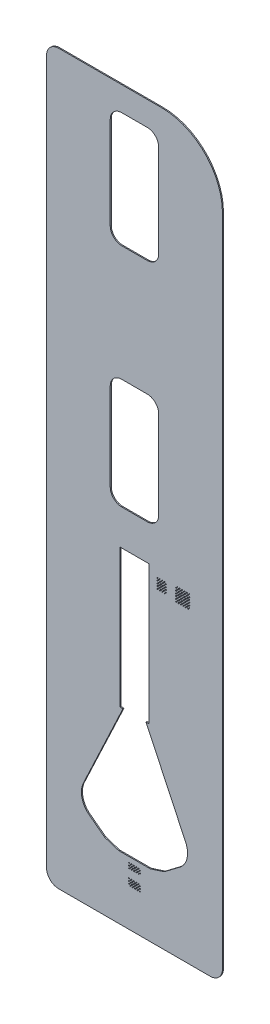
SolidWorks part; units mm, degrees
material "3M 9474LE (300LSE)"
ref_plane "Front Plane" through (0, 0, 0) normal (0, 0, 1) x (1, 0, 0)
ref_plane "Top Plane" through (0, 0, 0) normal (0, 1, 0) x (1, 0, 0)
ref_plane "Right Plane" through (0, 0, 0) normal (1, 0, 0) x (0, 0, -1)
sketch "Sketch3" plane through (0, 0, 0) normal (0, 0, 1) x (1, 0, 0)
  line L0 (0, 60) -> (0, -60) construction
  line L1 (-12.5, 60) -> (4.5, 60)
  line L2 (-14.5, 58) -> (-14.5, -58)
  line L3 (-12.5, -60) -> (12.5, -60)
  line L4 (14.5, 50) -> (14.5, -58)
  line L5 (-14.5, 60) -> (14.5, -60) construction
  line L6 (-14.5, -60) -> (14.5, 60) construction
  line L7 (-14.5, 0) -> (14.5, 0) construction
  line L8 (0, -55) -> (0, 55) construction
  arc A0 (-14.5, -58) -> (-12.5, -60) centre (-12.5, -58) ccw
  arc A1 (12.5, -60) -> (14.5, -58) centre (12.5, -58) ccw
  arc A2 (4.5, 60) -> (14.5, 50) centre (4.5, 50) cw
  arc A3 (-12.5, 60) -> (-14.5, 58) centre (-12.5, 58) ccw
  point P0 (0, 0)
extrude "Boss-Extrude2" add sketch "Sketch3" along normal blind 0.17
sketch "Sketch4" plane through (0, 0, 0.17) normal (0, 0, 1) x (1, 0, 0)
  line L10 (-7.4, -46.9731) -> (-4.925, -48.85) construction
  line L30 (-4.925, -48.85) -> (-2.6, -49.6) construction
  line L36 (-2.6, -49.6) -> (2.6, -49.6) construction
  line L46 (2.6, -49.6) -> (4.925, -48.85) construction
  line L47 (4.925, -48.85) -> (7.4, -46.9731) construction
  line L48 (-1.9, -29) -> (-8.375, -42.75) construction
  line L55 (8.375, -42.75) -> (1.9, -29) construction
  line L57 (1.9, -29) -> (2.4, -29) construction
  line L59 (-2.4, -29) -> (-1.9, -29) construction
  line L62 (-2.4, -6.15) -> (-2.4, -29) construction
  line L69 (2.4, -29) -> (2.4, -6.15) construction
  line L79 (2.4, -6.15) -> (-2.4, -6.15) construction
  line L80 (-4, 16.0318) -> (-4, 1.6) construction
  line L81 (-2.1, -0.3) -> (2.1, -0.3) construction
  line L82 (4, 1.6) -> (4, 16.0318) construction
  line L83 (2.1, 17.9318) -> (-2.1, 17.9318) construction
  line L91 (-2.1, 37) -> (2.1, 37) construction
  line L92 (4, 38.9) -> (4, 54.1) construction
  line L107 (2.1, 56) -> (-2.1, 56) construction
  line L108 (-4, 54.1) -> (-4, 38.9) construction
  line L109 (-7.4, -46.9731) -> (-4.925, -48.85)
  line L110 (-4.925, -48.85) -> (-2.6, -49.6)
  line L111 (-2.6, -49.6) -> (2.6, -49.6)
  line L112 (2.6, -49.6) -> (4.925, -48.85)
  line L113 (4.925, -48.85) -> (7.4, -46.9731)
  line L114 (-1.9, -29) -> (-8.375, -42.75)
  line L115 (8.375, -42.75) -> (1.9, -29)
  line L116 (1.9, -29) -> (2.4, -29)
  line L117 (-2.4, -29) -> (-1.9, -29)
  line L118 (-2.4, -6.15) -> (-2.4, -29)
  line L119 (2.4, -29) -> (2.4, -6.15)
  line L120 (2.4, -6.15) -> (-2.4, -6.15)
  line L121 (-4, 16.0318) -> (-4, 1.6)
  line L122 (-2.1, -0.3) -> (2.1, -0.3)
  line L123 (4, 1.6) -> (4, 16.0318)
  line L124 (2.1, 17.9318) -> (-2.1, 17.9318)
  line L125 (-2.1, 37) -> (2.1, 37)
  line L126 (4, 38.9) -> (4, 54.1)
  line L127 (2.1, 56) -> (-2.1, 56)
  line L128 (-4, 54.1) -> (-4, 38.9)
  arc A134 (-4, 1.6) -> (-2.1, -0.3) centre (-2.1, 1.6) ccw construction
  arc A135 (2.1, -0.3) -> (4, 1.6) centre (2.1, 1.6) ccw construction
  arc A136 (4, 16.0318) -> (2.1, 17.9318) centre (2.1, 16.0318) ccw construction
  arc A137 (-2.1, 17.9318) -> (-4, 16.0318) centre (-2.1, 16.0318) ccw construction
  arc A138 (-4, 38.9) -> (-2.1, 37) centre (-2.1, 38.9) ccw construction
  arc A139 (2.1, 37) -> (4, 38.9) centre (2.1, 38.9) ccw construction
  arc A140 (4, 54.1) -> (2.1, 56) centre (2.1, 54.1) ccw construction
  arc A141 (-2.1, 56) -> (-4, 54.1) centre (-2.1, 54.1) ccw construction
  arc A142 (-4, 1.6) -> (-2.1, -0.3) centre (-2.1, 1.6) ccw
  arc A143 (2.1, -0.3) -> (4, 1.6) centre (2.1, 1.6) ccw
  arc A144 (4, 16.0318) -> (2.1, 17.9318) centre (2.1, 16.0318) ccw
  arc A145 (-2.1, 17.9318) -> (-4, 16.0318) centre (-2.1, 16.0318) ccw
  arc A146 (-4, 38.9) -> (-2.1, 37) centre (-2.1, 38.9) ccw
  arc A147 (2.1, 37) -> (4, 38.9) centre (2.1, 38.9) ccw
  arc A148 (4, 54.1) -> (2.1, 56) centre (2.1, 54.1) ccw
  arc A149 (-2.1, 56) -> (-4, 54.1) centre (-2.1, 54.1) ccw
  spline S0 degree 3 poles (-1836.1355, -3592.7026) (2222.5014, 3309.4868) (-2600.2291, -3121.4243) (2902.6094, 2687.0541) knots -40.180202 -40.180202 -40.180202 -40.180202 44.080876 44.080876 44.080876 44.080876 only from (-8.375, -42.75) to (-8.75, -44.3) construction
  spline S1 degree 3 poles (3156.3673, -2476.859) (-2885.9846, 2765.5821) (2531.5071, -3169.0107) (-2157.875, 3316.9521) knots -17.902772 -17.902772 -17.902772 -17.902772 25.226336 25.226336 25.226336 25.226336 only from (-8.75, -44.3) to (-7.4, -46.9731) construction
  spline S2 degree 3 poles (2157.885, 3316.966) (-2531.5149, -3169.0192) (2885.9891, 2765.586) (-3156.3676, -2476.8592) knots -18.228062 -18.228062 -18.228062 -18.228062 24.901077 24.901077 24.901077 24.901077 only from (7.4, -46.9731) to (8.75, -44.3) construction
  spline S3 degree 3 poles (-2902.6247, 2687.0702) (2600.2145, -3121.4114) (-2222.4639, 3309.4382) (1836.0834, -3592.6141) knots -39.080954 -39.080954 -39.080954 -39.080954 45.179842 45.179842 45.179842 45.179842 only from (8.75, -44.3) to (8.375, -42.75) construction
  spline S4 degree 3 poles (-8.375, -42.75) (-8.614, -43.206) (-8.7497, -43.7369) (-8.75, -44.3) knots 2 2 2 2 3 3 3 3
  spline S5 degree 3 poles (-8.75, -44.3) (-8.7506, -45.4277) (-8.2114, -46.4163) (-7.4, -46.9731) knots 3 3 3 3 3.998305 3.998305 3.998305 3.998305
  spline S6 degree 3 poles (7.4, -46.9731) (8.2114, -46.4163) (8.7506, -45.4277) (8.75, -44.3) knots 3 3 3 3 3.998305 3.998305 3.998305 3.998305
  spline S7 degree 3 poles (8.75, -44.3) (8.7497, -43.7369) (8.614, -43.206) (8.375, -42.75) knots 2 2 2 2 3 3 3 3
extrude "Cut-Extrude1" cut sketch "Sketch4" against normal through all contours L127 A149 L128 A146 L125 A147 L126 A148 | L124 A145 L121 A142 L122 A143 L123 A144 | S6 S7 L115 L116 L119 L120 L118 L117 L114 S4 S5 L109 L110 L111 L112 L113
sketch "Sketch5" plane through (0, 0, 0.17) normal (0, 0, 1) x (1, 0, 0)
  line L0 (-0.1, -50.9) -> (0.1, -50.7) construction
  line L1 (-0.9, -50.5) -> (-0.9, -50.9) construction
  line L2 (0, -50.6) -> (0, -53.6) construction
  line L3 (0.75, -50.6) -> (-0.75, -50.6) construction
  line L4 (-0.75, -53.6) -> (0.75, -53.6) construction
  line L7 (-0.9, -52.7) -> (-0.9, -53.1) construction
  line L8 (-0.1, -50.5) -> (0.1, -50.7) construction
  line L9 (-0.1, -53.5) -> (0.1, -53.7) construction
  circle A0 centre (-0.9, -50.5) radius 0.075
  circle A1 centre (-0.7, -50.5) radius 0.075 [skipped]
  circle A2 centre (-0.5, -50.5) radius 0.075
  circle A3 centre (-0.3, -50.5) radius 0.075 [skipped]
  circle A4 centre (-0.1, -50.5) radius 0.075
  circle A5 centre (0.1, -50.5) radius 0.075 [skipped]
  circle A6 centre (0.3, -50.5) radius 0.075
  circle A7 centre (0.5, -50.5) radius 0.075 [skipped]
  circle A8 centre (0.7, -50.5) radius 0.075
  circle A9 centre (0.9, -50.5) radius 0.075 [skipped]
  circle A11 centre (-0.7, -50.7) radius 0.075
  circle A12 centre (-0.5, -50.7) radius 0.075 [skipped]
  circle A13 centre (-0.3, -50.7) radius 0.075
  circle A14 centre (-0.1, -50.7) radius 0.075 [skipped]
  circle A15 centre (0.1, -50.7) radius 0.075
  circle A16 centre (0.3, -50.7) radius 0.075 [skipped]
  circle A17 centre (0.5, -50.7) radius 0.075
  circle A18 centre (0.7, -50.7) radius 0.075 [skipped]
  circle A19 centre (0.9, -50.7) radius 0.075
  circle A20 centre (-0.9, -52.7) radius 0.075
  circle A21 centre (-0.7, -50.9) radius 0.075 [skipped]
  circle A22 centre (-0.5, -50.9) radius 0.075
  circle A23 centre (-0.3, -50.9) radius 0.075 [skipped]
  circle A24 centre (-0.1, -50.9) radius 0.075
  circle A25 centre (0.1, -50.9) radius 0.075 [skipped]
  circle A26 centre (0.3, -50.9) radius 0.075
  circle A27 centre (0.5, -50.9) radius 0.075 [skipped]
  circle A28 centre (0.7, -50.9) radius 0.075
  circle A29 centre (0.9, -50.9) radius 0.075 [skipped]
  circle A31 centre (-0.7, -51.1) radius 0.075
  circle A32 centre (-0.5, -51.1) radius 0.075 [skipped]
  circle A33 centre (-0.3, -51.1) radius 0.075
  circle A34 centre (-0.1, -51.1) radius 0.075 [skipped]
  circle A35 centre (0.1, -51.1) radius 0.075
  circle A36 centre (0.3, -51.1) radius 0.075 [skipped]
  circle A37 centre (0.5, -51.1) radius 0.075
  circle A38 centre (0.7, -51.1) radius 0.075 [skipped]
  circle A39 centre (0.9, -51.1) radius 0.075
  circle A40 centre (-0.7, -52.7) radius 0.075 [skipped]
  circle A41 centre (-0.7, -51.3) radius 0.075 [skipped]
  circle A42 centre (-0.5, -51.3) radius 0.075
  circle A43 centre (-0.3, -51.3) radius 0.075 [skipped]
  circle A44 centre (-0.1, -51.3) radius 0.075
  circle A45 centre (0.1, -51.3) radius 0.075 [skipped]
  circle A46 centre (0.3, -51.3) radius 0.075
  circle A47 centre (0.5, -51.3) radius 0.075 [skipped]
  circle A48 centre (0.7, -51.3) radius 0.075
  circle A49 centre (0.9, -51.3) radius 0.075 [skipped]
  circle A51 centre (-0.9, -50.7) radius 0.075 [skipped]
  circle A52 centre (-0.9, -50.9) radius 0.075
  circle A53 centre (-0.9, -51.1) radius 0.075 [skipped]
  circle A54 centre (-0.9, -51.3) radius 0.075
  circle A55 centre (-0.5, -52.7) radius 0.075
  circle A56 centre (-0.3, -52.7) radius 0.075 [skipped]
  circle A57 centre (-0.1, -52.7) radius 0.075
  circle A58 centre (0.1, -52.7) radius 0.075 [skipped]
  circle A59 centre (0.3, -52.7) radius 0.075
  circle A60 centre (0.5, -52.7) radius 0.075 [skipped]
  circle A61 centre (0.7, -52.7) radius 0.075
  circle A62 centre (0.9, -52.7) radius 0.075 [skipped]
  circle A63 centre (-0.7, -52.9) radius 0.075
  circle A64 centre (-0.5, -52.9) radius 0.075 [skipped]
  circle A65 centre (-0.3, -52.9) radius 0.075
  circle A66 centre (-0.1, -52.9) radius 0.075 [skipped]
  circle A67 centre (0.1, -52.9) radius 0.075
  circle A68 centre (0.3, -52.9) radius 0.075 [skipped]
  circle A69 centre (0.5, -52.9) radius 0.075
  circle A70 centre (0.7, -52.9) radius 0.075 [skipped]
  circle A71 centre (0.9, -52.9) radius 0.075
  circle A72 centre (-0.7, -53.1) radius 0.075 [skipped]
  circle A73 centre (-0.5, -53.1) radius 0.075
  circle A74 centre (-0.3, -53.1) radius 0.075 [skipped]
  circle A75 centre (-0.1, -53.1) radius 0.075
  circle A76 centre (0.1, -53.1) radius 0.075 [skipped]
  circle A77 centre (0.3, -53.1) radius 0.075
  circle A78 centre (0.5, -53.1) radius 0.075 [skipped]
  circle A79 centre (0.7, -53.1) radius 0.075
  circle A80 centre (0.9, -53.1) radius 0.075 [skipped]
  circle A81 centre (-0.7, -53.3) radius 0.075
  circle A82 centre (-0.5, -53.3) radius 0.075 [skipped]
  circle A83 centre (-0.3, -53.3) radius 0.075
  circle A84 centre (-0.1, -53.3) radius 0.075 [skipped]
  circle A85 centre (0.1, -53.3) radius 0.075
  circle A86 centre (0.3, -53.3) radius 0.075 [skipped]
  circle A87 centre (0.5, -53.3) radius 0.075
  circle A88 centre (0.7, -53.3) radius 0.075 [skipped]
  circle A89 centre (0.9, -53.3) radius 0.075
  circle A90 centre (-0.7, -53.5) radius 0.075 [skipped]
  circle A91 centre (-0.5, -53.5) radius 0.075
  circle A92 centre (-0.3, -53.5) radius 0.075 [skipped]
  circle A93 centre (-0.1, -53.5) radius 0.075
  circle A94 centre (0.1, -53.5) radius 0.075 [skipped]
  circle A95 centre (0.3, -53.5) radius 0.075
  circle A96 centre (0.5, -53.5) radius 0.075 [skipped]
  circle A97 centre (0.7, -53.5) radius 0.075
  circle A98 centre (0.9, -53.5) radius 0.075 [skipped]
  circle A99 centre (-0.7, -53.7) radius 0.075
  circle A100 centre (-0.5, -53.7) radius 0.075 [skipped]
  circle A101 centre (-0.3, -53.7) radius 0.075
  circle A102 centre (-0.1, -53.7) radius 0.075 [skipped]
  circle A103 centre (0.1, -53.7) radius 0.075
  circle A104 centre (0.3, -53.7) radius 0.075 [skipped]
  circle A105 centre (0.5, -53.7) radius 0.075
  circle A106 centre (0.7, -53.7) radius 0.075 [skipped]
  circle A107 centre (0.9, -53.7) radius 0.075
  circle A108 centre (-0.9, -52.9) radius 0.075 [skipped]
  circle A109 centre (-0.9, -53.1) radius 0.075
  circle A110 centre (-0.9, -53.3) radius 0.075 [skipped]
  circle A111 centre (-0.9, -53.5) radius 0.075
  circle A112 centre (-0.9, -53.7) radius 0.075 [skipped]
  point P2 (0, -50.8)
  point P4 (0, -50.6)
  point P229 (0, -53.6)
  dimension "D1" = 0.15
  dimension "D4" = 0.4
  dimension "D5" = 0.4
  dimension "D6" = 0.4
  dimension "D9" = 0.4
  dimension "D2" = 10
  dimension "D3" = 5
  dimension "D7" = 10
  dimension "D8" = 6
extrude "Cut-Extrude2" cut sketch "Sketch5" against normal through all
sketch "Sketch6" plane through (0, 0, 0.17) normal (0, 0, 1) x (1, 0, 0)
  line L0 (4.08, -8.27) -> (8.74, -8.27) construction
  line L1 (4.08, -7.47) -> (4.08, -9.07) construction
  line L2 (8.74, -9.07) -> (8.74, -7.47) construction
  line L3 (3.98, -8.07) -> (4.18, -8.27) construction
  line L4 (3.78, -9.07) -> (4.18, -9.07) construction
  line L5 (3.78, -9.07) -> (3.78, -8.67) construction
  line L6 (6.84, -9.37) -> (7.24, -9.37) construction
  line L7 (6.84, -9.37) -> (6.84, -8.97) construction
  line L8 (8.84, -8.17) -> (8.64, -8.37) construction
  circle A0 centre (3.78, -9.07) radius 0.075
  circle A1 centre (3.98, -9.07) radius 0.075 [skipped]
  circle A2 centre (4.18, -9.07) radius 0.075
  circle A3 centre (4.38, -9.07) radius 0.075 [skipped]
  circle A4 centre (4.58, -9.07) radius 0.075
  circle A5 centre (4.78, -9.07) radius 0.075 [skipped]
  circle A6 centre (4.98, -9.07) radius 0.075
  circle A7 centre (5.18, -9.07) radius 0.075 [skipped]
  circle A8 centre (3.98, -8.87) radius 0.075
  circle A9 centre (4.18, -8.87) radius 0.075 [skipped]
  circle A10 centre (4.38, -8.87) radius 0.075
  circle A11 centre (4.58, -8.87) radius 0.075 [skipped]
  circle A12 centre (4.78, -8.87) radius 0.075
  circle A13 centre (4.98, -8.87) radius 0.075 [skipped]
  circle A14 centre (5.18, -8.87) radius 0.075
  circle A15 centre (3.98, -8.67) radius 0.075 [skipped]
  circle A16 centre (4.18, -8.67) radius 0.075
  circle A17 centre (4.38, -8.67) radius 0.075 [skipped]
  circle A18 centre (4.58, -8.67) radius 0.075
  circle A19 centre (4.78, -8.67) radius 0.075 [skipped]
  circle A20 centre (4.98, -8.67) radius 0.075
  circle A21 centre (5.18, -8.67) radius 0.075 [skipped]
  circle A22 centre (3.98, -8.47) radius 0.075
  circle A23 centre (4.18, -8.47) radius 0.075 [skipped]
  circle A24 centre (4.38, -8.47) radius 0.075
  circle A25 centre (4.58, -8.47) radius 0.075 [skipped]
  circle A26 centre (4.78, -8.47) radius 0.075
  circle A27 centre (4.98, -8.47) radius 0.075 [skipped]
  circle A28 centre (5.18, -8.47) radius 0.075
  circle A29 centre (3.98, -8.27) radius 0.075 [skipped]
  circle A30 centre (4.18, -8.27) radius 0.075
  circle A31 centre (4.38, -8.27) radius 0.075 [skipped]
  circle A32 centre (4.58, -8.27) radius 0.075
  circle A33 centre (4.78, -8.27) radius 0.075 [skipped]
  circle A34 centre (4.98, -8.27) radius 0.075
  circle A35 centre (5.18, -8.27) radius 0.075 [skipped]
  circle A36 centre (3.98, -8.07) radius 0.075
  circle A37 centre (4.18, -8.07) radius 0.075 [skipped]
  circle A38 centre (4.38, -8.07) radius 0.075
  circle A39 centre (4.58, -8.07) radius 0.075 [skipped]
  circle A40 centre (4.78, -8.07) radius 0.075
  circle A41 centre (4.98, -8.07) radius 0.075 [skipped]
  circle A42 centre (5.18, -8.07) radius 0.075
  circle A43 centre (3.98, -7.87) radius 0.075 [skipped]
  circle A44 centre (4.18, -7.87) radius 0.075
  circle A45 centre (4.38, -7.87) radius 0.075 [skipped]
  circle A46 centre (4.58, -7.87) radius 0.075
  circle A47 centre (4.78, -7.87) radius 0.075 [skipped]
  circle A48 centre (4.98, -7.87) radius 0.075
  circle A49 centre (5.18, -7.87) radius 0.075 [skipped]
  circle A50 centre (3.98, -7.67) radius 0.075
  circle A51 centre (4.18, -7.67) radius 0.075 [skipped]
  circle A52 centre (4.38, -7.67) radius 0.075
  circle A53 centre (4.58, -7.67) radius 0.075 [skipped]
  circle A54 centre (4.78, -7.67) radius 0.075
  circle A55 centre (4.98, -7.67) radius 0.075 [skipped]
  circle A56 centre (5.18, -7.67) radius 0.075
  circle A57 centre (3.98, -7.47) radius 0.075 [skipped]
  circle A58 centre (4.18, -7.47) radius 0.075
  circle A59 centre (4.38, -7.47) radius 0.075 [skipped]
  circle A60 centre (4.58, -7.47) radius 0.075
  circle A61 centre (4.78, -7.47) radius 0.075 [skipped]
  circle A62 centre (4.98, -7.47) radius 0.075
  circle A63 centre (5.18, -7.47) radius 0.075 [skipped]
  circle A64 centre (3.78, -8.87) radius 0.075 [skipped]
  circle A65 centre (3.78, -8.67) radius 0.075
  circle A66 centre (3.78, -8.47) radius 0.075 [skipped]
  circle A67 centre (3.78, -8.27) radius 0.075
  circle A68 centre (3.78, -8.07) radius 0.075 [skipped]
  circle A69 centre (3.78, -7.87) radius 0.075
  circle A70 centre (3.78, -7.67) radius 0.075 [skipped]
  circle A71 centre (3.78, -7.47) radius 0.075
  circle A72 centre (6.84, -9.37) radius 0.075
  circle A73 centre (7.04, -9.37) radius 0.075 [skipped]
  circle A74 centre (7.24, -9.37) radius 0.075
  circle A75 centre (7.44, -9.37) radius 0.075 [skipped]
  circle A76 centre (7.64, -9.37) radius 0.075
  circle A77 centre (7.84, -9.37) radius 0.075 [skipped]
  circle A78 centre (8.04, -9.37) radius 0.075
  circle A79 centre (8.24, -9.37) radius 0.075 [skipped]
  circle A80 centre (8.44, -9.37) radius 0.075
  circle A81 centre (8.64, -9.37) radius 0.075 [skipped]
  circle A82 centre (8.84, -9.37) radius 0.075
  circle A83 centre (9.04, -9.37) radius 0.075 [skipped]
  circle A84 centre (7.04, -9.17) radius 0.075
  circle A85 centre (7.24, -9.17) radius 0.075 [skipped]
  circle A86 centre (7.44, -9.17) radius 0.075
  circle A87 centre (7.64, -9.17) radius 0.075 [skipped]
  circle A88 centre (7.84, -9.17) radius 0.075
  circle A89 centre (8.04, -9.17) radius 0.075 [skipped]
  circle A90 centre (8.24, -9.17) radius 0.075
  circle A91 centre (8.44, -9.17) radius 0.075 [skipped]
  circle A92 centre (8.64, -9.17) radius 0.075
  circle A93 centre (8.84, -9.17) radius 0.075 [skipped]
  circle A94 centre (9.04, -9.17) radius 0.075
  circle A95 centre (7.04, -8.97) radius 0.075 [skipped]
  circle A96 centre (7.24, -8.97) radius 0.075
  circle A97 centre (7.44, -8.97) radius 0.075 [skipped]
  circle A98 centre (7.64, -8.97) radius 0.075
  circle A99 centre (7.84, -8.97) radius 0.075 [skipped]
  circle A100 centre (8.04, -8.97) radius 0.075
  circle A101 centre (8.24, -8.97) radius 0.075 [skipped]
  circle A102 centre (8.44, -8.97) radius 0.075
  circle A103 centre (8.64, -8.97) radius 0.075 [skipped]
  circle A104 centre (8.84, -8.97) radius 0.075
  circle A105 centre (9.04, -8.97) radius 0.075 [skipped]
  circle A106 centre (7.04, -8.77) radius 0.075
  circle A107 centre (7.24, -8.77) radius 0.075 [skipped]
  circle A108 centre (7.44, -8.77) radius 0.075
  circle A109 centre (7.64, -8.77) radius 0.075 [skipped]
  circle A110 centre (7.84, -8.77) radius 0.075
  circle A111 centre (8.04, -8.77) radius 0.075 [skipped]
  circle A112 centre (8.24, -8.77) radius 0.075
  circle A113 centre (8.44, -8.77) radius 0.075 [skipped]
  circle A114 centre (8.64, -8.77) radius 0.075
  circle A116 centre (9.04, -8.77) radius 0.075
  circle A117 centre (7.04, -8.57) radius 0.075 [skipped]
  circle A118 centre (7.24, -8.57) radius 0.075
  circle A119 centre (7.44, -8.57) radius 0.075 [skipped]
  circle A120 centre (7.64, -8.57) radius 0.075
  circle A121 centre (7.84, -8.57) radius 0.075 [skipped]
  circle A122 centre (8.04, -8.57) radius 0.075
  circle A123 centre (8.24, -8.57) radius 0.075 [skipped]
  circle A124 centre (8.44, -8.57) radius 0.075
  circle A125 centre (8.64, -8.57) radius 0.075 [skipped]
  circle A126 centre (8.84, -8.57) radius 0.075
  circle A127 centre (9.04, -8.57) radius 0.075 [skipped]
  circle A128 centre (7.04, -8.37) radius 0.075
  circle A129 centre (7.24, -8.37) radius 0.075 [skipped]
  circle A130 centre (7.44, -8.37) radius 0.075
  circle A131 centre (7.64, -8.37) radius 0.075 [skipped]
  circle A132 centre (7.84, -8.37) radius 0.075
  circle A133 centre (8.04, -8.37) radius 0.075 [skipped]
  circle A134 centre (8.24, -8.37) radius 0.075
  circle A135 centre (8.44, -8.37) radius 0.075 [skipped]
  circle A136 centre (8.64, -8.37) radius 0.075
  circle A137 centre (8.84, -8.37) radius 0.075 [skipped]
  circle A138 centre (9.04, -8.37) radius 0.075
  circle A139 centre (7.04, -8.17) radius 0.075 [skipped]
  circle A140 centre (7.24, -8.17) radius 0.075
  circle A141 centre (7.44, -8.17) radius 0.075 [skipped]
  circle A142 centre (7.64, -8.17) radius 0.075
  circle A143 centre (7.84, -8.17) radius 0.075 [skipped]
  circle A144 centre (8.04, -8.17) radius 0.075
  circle A145 centre (8.24, -8.17) radius 0.075 [skipped]
  circle A146 centre (8.44, -8.17) radius 0.075
  circle A147 centre (8.64, -8.17) radius 0.075 [skipped]
  circle A148 centre (8.84, -8.17) radius 0.075
  circle A149 centre (9.04, -8.17) radius 0.075 [skipped]
  circle A150 centre (7.04, -7.97) radius 0.075
  circle A151 centre (7.24, -7.97) radius 0.075 [skipped]
  circle A152 centre (7.44, -7.97) radius 0.075
  circle A153 centre (7.64, -7.97) radius 0.075 [skipped]
  circle A154 centre (7.84, -7.97) radius 0.075
  circle A155 centre (8.04, -7.97) radius 0.075 [skipped]
  circle A156 centre (8.24, -7.97) radius 0.075
  circle A157 centre (8.44, -7.97) radius 0.075 [skipped]
  circle A158 centre (8.64, -7.97) radius 0.075
  circle A159 centre (8.84, -7.97) radius 0.075 [skipped]
  circle A160 centre (9.04, -7.97) radius 0.075
  circle A161 centre (7.04, -7.77) radius 0.075 [skipped]
  circle A162 centre (7.24, -7.77) radius 0.075
  circle A163 centre (7.44, -7.77) radius 0.075 [skipped]
  circle A164 centre (7.64, -7.77) radius 0.075
  circle A165 centre (7.84, -7.77) radius 0.075 [skipped]
  circle A166 centre (8.04, -7.77) radius 0.075
  circle A167 centre (8.24, -7.77) radius 0.075 [skipped]
  circle A168 centre (8.44, -7.77) radius 0.075
  circle A169 centre (8.64, -7.77) radius 0.075 [skipped]
  circle A170 centre (8.84, -7.77) radius 0.075
  circle A171 centre (9.04, -7.77) radius 0.075 [skipped]
  circle A172 centre (7.04, -7.57) radius 0.075
  circle A173 centre (7.24, -7.57) radius 0.075 [skipped]
  circle A174 centre (7.44, -7.57) radius 0.075
  circle A175 centre (7.64, -7.57) radius 0.075 [skipped]
  circle A176 centre (7.84, -7.57) radius 0.075
  circle A177 centre (8.04, -7.57) radius 0.075 [skipped]
  circle A178 centre (8.24, -7.57) radius 0.075
  circle A179 centre (8.44, -7.57) radius 0.075 [skipped]
  circle A180 centre (8.64, -7.57) radius 0.075
  circle A181 centre (8.84, -7.57) radius 0.075 [skipped]
  circle A182 centre (9.04, -7.57) radius 0.075
  circle A183 centre (7.04, -7.37) radius 0.075 [skipped]
  circle A184 centre (7.24, -7.37) radius 0.075
  circle A185 centre (7.44, -7.37) radius 0.075 [skipped]
  circle A186 centre (7.64, -7.37) radius 0.075
  circle A187 centre (7.84, -7.37) radius 0.075 [skipped]
  circle A188 centre (8.04, -7.37) radius 0.075
  circle A189 centre (8.24, -7.37) radius 0.075 [skipped]
  circle A190 centre (8.44, -7.37) radius 0.075
  circle A191 centre (8.64, -7.37) radius 0.075 [skipped]
  circle A192 centre (8.84, -7.37) radius 0.075
  circle A193 centre (9.04, -7.37) radius 0.075 [skipped]
  circle A194 centre (7.04, -7.17) radius 0.075
  circle A195 centre (7.24, -7.17) radius 0.075 [skipped]
  circle A196 centre (7.44, -7.17) radius 0.075
  circle A197 centre (7.64, -7.17) radius 0.075 [skipped]
  circle A198 centre (7.84, -7.17) radius 0.075
  circle A199 centre (8.04, -7.17) radius 0.075 [skipped]
  circle A200 centre (8.24, -7.17) radius 0.075
  circle A201 centre (8.44, -7.17) radius 0.075 [skipped]
  circle A202 centre (8.64, -7.17) radius 0.075
  circle A203 centre (8.84, -7.17) radius 0.075 [skipped]
  circle A204 centre (9.04, -7.17) radius 0.075
  circle A205 centre (6.84, -9.17) radius 0.075 [skipped]
  circle A206 centre (6.84, -8.97) radius 0.075
  circle A207 centre (6.84, -8.77) radius 0.075 [skipped]
  circle A208 centre (6.84, -8.57) radius 0.075
  circle A209 centre (6.84, -8.37) radius 0.075 [skipped]
  circle A210 centre (6.84, -8.17) radius 0.075
  circle A211 centre (6.84, -7.97) radius 0.075 [skipped]
  circle A212 centre (6.84, -7.77) radius 0.075
  circle A213 centre (6.84, -7.57) radius 0.075 [skipped]
  circle A214 centre (6.84, -7.37) radius 0.075
  circle A215 centre (6.84, -7.17) radius 0.075 [skipped]
  circle A216 centre (8.84, -8.77) radius 0.075 [skipped]
  point P151 (4.08, -8.17)
  point P153 (8.74, -8.27)
  dimension "D1" = 0.15
  dimension "D2" = 9
  dimension "D3" = 0.4
  dimension "D4" = 0.4
  dimension "D8" = 0.4
  dimension "D9" = 0.4
  dimension "D5" = 8
  dimension "D7" = 12
  dimension "D6" = 12
extrude "Cut-Extrude3" cut sketch "Sketch6" against normal through all
